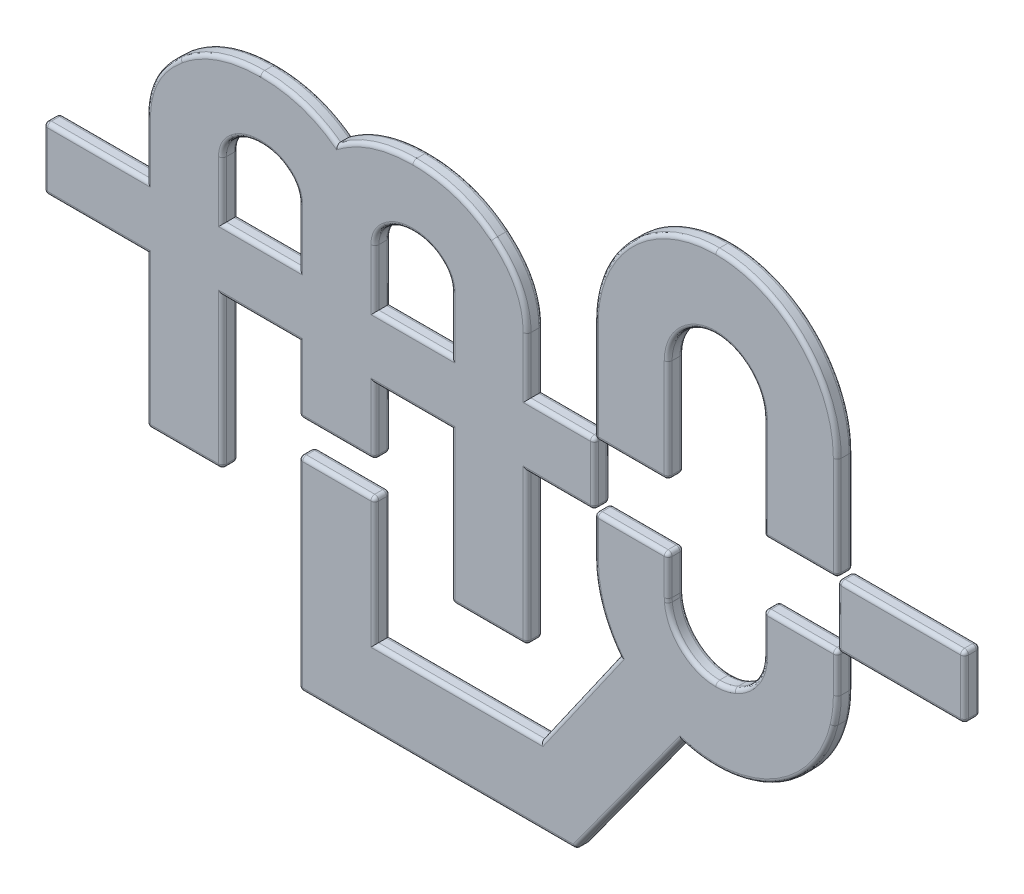
SolidWorks part; units mm, degrees
material "ABS"
ref_plane "Plano frontal" through (0, 0, 0) normal (0, 0, 1) x (1, 0, 0)
ref_plane "Plano superior" through (0, 0, 0) normal (0, 1, 0) x (1, 0, 0)
ref_plane "Plano direito" through (0, 0, 0) normal (1, 0, 0) x (0, 0, -1)
sketch "Esboço1" plane through (0, 0, 0) normal (0, 0, 1) x (1, 0, 0)
  line L0 (20.3706, -29.3615) -> (15.5406, -29.3604)
  line L3 (15.5406, -29.3604) -> (15.5406, -25.7678)
  line L4 (39.1028, -29.3604) -> (39.1028, -33.3385)
  line L5 (39.1028, -29.3604) -> (39.1028, -22.8429)
  line L6 (54.495, -33.3385) -> (62.5568, -33.3385)
  line L7 (62.5568, -33.3385) -> (62.5568, -29.3604)
  line L8 (62.5568, -29.3604) -> (54.495, -29.3604)
  line L9 (54.495, -33.3385) -> (54.495, -35.841)
  line L10 (44.6225, -43.2216) -> (37.8938, -52.503)
  line L11 (37.8938, -52.503) -> (20.3712, -52.5003)
  line L12 (20.3712, -52.5003) -> (20.3712, -39.5946)
  line L14 (-4.5162, 7.0505) -> (71.2838, 7.0505)
  line L15 (-4.5162, 7.0505) -> (-4.5162, -69.7495)
  line L16 (-4.5162, -69.7495) -> (71.2838, -69.7495)
  line L17 (71.2838, 7.0505) -> (71.2838, -69.7495)
  line L21 (16.0406, -28.8605) -> (16.0406, -25.7678)
  line L22 (19.8712, -25.7677) -> (19.8707, -28.8614)
  line L23 (19.8707, -28.8614) -> (16.0406, -28.8605)
  line L24 (25.6993, -25.7677) -> (25.7001, -28.8614)
  line L29 (-4.5162, 7.0505) -> (-4.5162, -69.7495)
  line L30 (-4.5162, -69.7495) -> (71.2838, -69.7495)
  line L31 (71.2838, -69.7495) -> (71.2838, 7.0505)
  line L32 (71.2838, 7.0505) -> (-4.5162, 7.0505)
  line L33 (25.7001, -28.8614) -> (29.53, -28.8605)
  line L34 (29.53, -28.8605) -> (29.53, -25.7678)
  line L35 (39.6028, -32.8385) -> (44.2804, -32.8385)
  line L36 (44.2804, -33.3385) -> (44.2804, -35.841)
  line L37 (49.3174, -35.841) -> (49.3174, -32.8385)
  line L38 (49.3174, -32.8385) -> (53.995, -32.8385)
  line L39 (53.995, -32.8385) -> (53.995, -29.8604)
  line L40 (53.995, -29.8604) -> (49.3174, -29.8604)
  line L41 (49.3174, -29.8604) -> (49.3174, -22.8429)
  line L42 (44.2804, -22.8429) -> (44.2804, -29.8604)
  line L43 (44.2804, -29.8604) -> (39.6028, -29.8604)
  line L44 (39.6028, -29.8604) -> (39.6028, -32.8385)
  line L45 (38.6028, -33.3385) -> (38.6028, -35.841)
  line L46 (40.0744, -40.5146) -> (35.4557, -47.1142)
  line L47 (35.4557, -47.1142) -> (25.6888, -47.1142)
  line L48 (25.6888, -47.1142) -> (25.6888, -39.0946)
  line L49 (19.8712, -39.0946) -> (25.6888, -39.0946)
  line L50 (19.8712, -53.0002) -> (19.8712, -39.0946)
  line L51 (38.1489, -53.003) -> (19.8712, -53.0002)
  line L52 (44.8242, -43.7952) -> (38.1489, -53.003)
  line L53 (54.995, -33.8385) -> (54.995, -35.841)
  line L54 (54.995, -33.8385) -> (63.0568, -33.8385)
  line L55 (63.0568, -33.8385) -> (63.0568, -28.8604)
  line L56 (63.0568, -28.8604) -> (54.995, -28.8604)
  line L57 (54.995, -22.8429) -> (54.995, -28.8604)
  line L58 (38.6028, -28.8604) -> (38.6028, -22.8429)
  line L59 (35.3396, -28.8604) -> (38.6028, -28.8604)
  line L60 (35.3396, -25.7678) -> (35.3396, -28.8604)
  line L61 (10.2309, -25.7678) -> (10.2309, -28.8604)
  line L62 (3.7108, -28.8604) -> (10.2309, -28.8604)
  line L63 (3.7108, -33.8385) -> (3.7108, -28.8604)
  line L64 (10.2309, -33.8385) -> (3.7108, -33.8385)
  line L65 (10.2309, -43.3732) -> (10.2309, -33.8385)
  line L66 (16.0406, -43.3732) -> (10.2309, -43.3732)
  line L67 (16.0406, -33.8385) -> (16.0406, -43.3732)
  line L68 (19.8707, -33.8389) -> (16.0406, -33.8385)
  line L69 (19.8713, -38.0277) -> (19.8707, -33.8389)
  line L70 (25.6992, -38.0277) -> (19.8713, -38.0277)
  line L71 (25.6992, -38.0277) -> (25.7001, -33.8389)
  line L72 (25.7001, -33.8389) -> (29.53, -33.8385)
  line L73 (29.53, -33.8385) -> (29.53, -43.3732)
  line L74 (29.53, -43.3732) -> (35.3396, -43.3732)
  line L75 (35.3396, -43.3732) -> (35.3396, -33.8385)
  line L76 (35.3396, -33.8385) -> (39.1028, -33.8385)
  line L77 (39.6028, -29.8604) -> (39.6028, -33.3385) construction
  line L78 (39.1028, -32.8385) -> (44.2804, -32.8385) construction
  line L79 (44.2804, -32.8385) -> (44.2804, -35.841) construction
  line L80 (44.2804, -33.3385) -> (44.2804, -32.8385)
  line L189 (20.3712, -25.7678) -> (20.3706, -29.3615)
  line L190 (25.2002, -29.3615) -> (30.03, -29.3604)
  line L192 (30.03, -29.3604) -> (30.03, -25.7678)
  line L193 (25.1993, -25.7678) -> (25.2002, -29.3615)
  line L194 (20.3712, -37.5277) -> (20.3712, -39.5946) construction
  line L195 (20.3712, -39.5946) -> (25.1888, -39.5946)
  line L196 (25.1888, -39.5946) -> (25.1993, -37.5277) construction
  line L197 (25.1993, -37.5277) -> (20.3712, -37.5277)
  line L198 (25.1993, -37.5277) -> (25.2002, -33.3389)
  line L209 (43.7804, -22.8429) -> (43.7804, -29.3604)
  line L210 (49.8174, -29.3604) -> (49.8174, -22.8429)
  line L211 (54.495, -29.3604) -> (49.8174, -29.3604)
  line L212 (54.495, -33.3385) -> (54.495, -29.3604)
  line L213 (49.8174, -33.3385) -> (54.495, -33.3385)
  line L214 (49.8174, -35.841) -> (49.8174, -33.3385)
  line L215 (43.7804, -33.3385) -> (43.7804, -35.841)
  line L216 (39.1028, -33.3385) -> (43.7804, -33.3385)
  line L217 (39.1028, -29.3604) -> (39.1028, -33.3385) construction
  line L218 (43.7804, -29.3604) -> (39.1028, -29.3604)
  line L219 (25.2002, -33.3389) -> (30.03, -33.3385)
  line L221 (30.03, -33.3385) -> (30.03, -42.8732)
  line L222 (30.03, -42.8732) -> (34.8396, -42.8732)
  line L223 (34.8396, -42.8732) -> (34.8396, -33.3385)
  line L225 (34.8396, -33.3385) -> (39.1028, -33.3385)
  line L226 (40.6893, -40.508) -> (35.716, -47.6142)
  line L227 (35.716, -47.6142) -> (25.1888, -47.6142)
  line L228 (25.1888, -47.6142) -> (25.1888, -39.5946)
  line L230 (20.3712, -37.5277) -> (20.3706, -33.3389)
  line L232 (39.1028, -33.3385) -> (39.1028, -35.841)
  line L233 (20.3706, -33.3389) -> (15.5406, -33.3385)
  line L234 (15.5406, -33.3385) -> (15.5406, -42.8732)
  line L235 (15.5406, -42.8732) -> (10.7309, -42.8732)
  line L236 (10.7309, -42.8732) -> (10.7309, -33.3385)
  line L238 (10.7309, -33.3385) -> (4.2108, -33.3385)
  line L239 (4.2108, -33.3385) -> (4.2108, -29.3604)
  line L240 (4.2108, -29.3604) -> (10.7309, -29.3604)
  line L241 (10.7309, -25.7678) -> (10.7309, -29.3604)
  line L242 (34.8396, -25.7678) -> (34.8396, -29.3604)
  line L243 (34.8396, -29.3604) -> (39.1028, -29.3604)
  line L244 (54.495, -22.8429) -> (54.495, -29.3604)
  spline S0 degree 1 poles (16.0406, -25.7678) (16.5619, -24.7584) knots 0 0 1 1 construction
  spline S1 degree 1 poles (16.5619, -24.7584) (17.9665, -24.2906) knots 0 0 1 1 construction
  spline S2 degree 1 poles (17.9665, -24.2906) (19.3573, -24.75) knots 0 0 1 1 construction
  spline S3 degree 1 poles (19.3573, -24.75) (19.8712, -25.7677) knots 0 0 1 1 construction
  spline S4 degree 3 poles (16.0406, -25.7678) (16.0406, -25.6734) (16.0617, -25.4788) (16.153, -25.2331) (16.3041, -24.9973) (16.4751, -24.8296) (16.5619, -24.7584) knots 8 8 8 8 8.249884 8.499767 8.749651 8.999535 8.999535 8.999535 8.999535
  spline S5 degree 3 poles (16.5619, -24.7584) (16.6555, -24.6821) (16.8576, -24.5445) (17.1847, -24.401) (17.5451, -24.3114) (17.8293, -24.2906) (17.9665, -24.2906) knots 9.000463 9.000463 9.000463 9.000463 9.250347 9.500232 9.750116 10 10 10 10
  spline S6 degree 3 poles (17.9665, -24.2906) (18.1005, -24.2906) (18.3773, -24.3109) (18.7336, -24.3986) (19.0598, -24.5397) (19.263, -24.675) (19.3573, -24.75) knots 10 10 10 10 10.24897 10.49794 10.74691 10.99588 10.99588 10.99588 10.99588
  spline S7 degree 3 poles (19.3573, -24.75) (19.4428, -24.8224) (19.6106, -24.9915) (19.76, -25.2299) (19.8504, -25.4781) (19.8712, -25.6731) (19.8712, -25.7677) knots 11.004142 11.004142 11.004142 11.004142 11.253098 11.502054 11.75101 11.999967 11.999967 11.999967 11.999967
  spline S11 degree 3 poles (44.6225, -43.2216) (45.3141, -43.4275) (46.0426, -43.5384) (46.7976, -43.5384) knots 10 10 10 10 11 11 11 11
  spline S12 degree 3 poles (54.2918, -37.5858) (54.4264, -37.0235) (54.495, -36.4402) (54.495, -35.841) knots 12 12 12 12 13 13 13 13
  spline S13 degree 3 poles (46.7976, -43.5384) (50.4325, -43.5384) (53.4999, -40.9884) (54.2918, -37.5858) knots 11 11 11 11 12 12 12 12
  spline S14 degree 1 poles (28.9981, -24.7504) (29.53, -25.7678) knots 0 0 1 1 construction
  spline S15 degree 1 poles (27.6041, -24.2906) (28.9981, -24.7504) knots 0 0 1 1 construction
  spline S16 degree 1 poles (26.2233, -24.7584) (27.6041, -24.2906) knots 0 0 1 1 construction
  spline S17 degree 1 poles (25.6993, -25.7677) (26.2233, -24.7584) knots 0 0 1 1 construction
  spline S18 degree 3 poles (29.53, -25.7678) (29.53, -25.6736) (29.5088, -25.4796) (29.4162, -25.2326) (29.2621, -24.994) (29.0869, -24.823) (28.9981, -24.7504) knots 17.999964 17.999964 17.999964 17.999964 18.249973 18.499982 18.749991 19 19 19 19
  spline S19 degree 3 poles (28.9981, -24.7504) (28.9066, -24.6755) (28.7091, -24.5411) (28.3854, -24.3996) (28.0264, -24.3113) (27.7415, -24.2906) (27.6041, -24.2906) knots 17 17 17 17 17.250009 17.500019 17.750028 18.000037 18.000037 18.000037 18.000037
  spline S20 degree 3 poles (27.6041, -24.2906) (27.4703, -24.2906) (27.1933, -24.3113) (26.84, -24.4005) (26.5178, -24.5436) (26.3164, -24.6821) (26.2233, -24.7584) knots 15.999619 15.999619 15.999619 15.999619 16.249714 16.499809 16.749905 17 17 17 17
  spline S21 degree 3 poles (26.2233, -24.7584) (26.1359, -24.8296) (25.9636, -24.9976) (25.812, -25.2332) (25.7205, -25.4786) (25.6993, -25.6734) (25.6993, -25.7677) knots 15.000046 15.000046 15.000046 15.000046 15.25013 15.500213 15.750297 16.00038 16.00038 16.00038 16.00038
  spline S22 degree 1 poles (44.2893, -36.0356) (46.7976, -38.3608) knots 0 0 1 1 construction
  spline S23 degree 1 poles (46.7976, -38.3608) (47.7651, -38.1567) knots 0 0 1 1 construction
  spline S24 degree 1 poles (47.7651, -38.1567) (48.8378, -37.2916) knots 0 0 1 1 construction
  spline S25 degree 1 poles (48.8378, -37.2916) (49.3174, -35.841) knots 0 0 1 1 construction
  spline S26 degree 1 poles (49.3174, -22.8429) (46.7976, -20.3257) knots 0 0 1 1 construction
  spline S27 degree 1 poles (46.7976, -20.3257) (44.2804, -22.8429) knots 0 0 1 1 construction
  spline S28 degree 3 poles (44.2893, -36.0356) (44.3144, -36.3459) (44.4904, -36.9638) (45.0612, -37.7175) (45.8506, -38.2323) (46.485, -38.3608) (46.7976, -38.3608) knots 3 3 3 3 3.25 3.5 3.75 4 4 4 4
  spline S29 degree 3 poles (46.7976, -38.3608) (46.8823, -38.3608) (47.0527, -38.3518) (47.2991, -38.3123) (47.5379, -38.2482) (47.6904, -38.1897) (47.7651, -38.1567) knots 2 2 2 2 2.250601 2.501202 2.751803 3.002404 3.002404 3.002404 3.002404
  spline S30 degree 3 poles (47.7651, -38.1567) (47.8715, -38.1112) (48.0783, -38.0051) (48.3631, -37.8046) (48.6198, -37.567) (48.7693, -37.3862) (48.8378, -37.2916) knots 0.998307 0.998307 0.998307 0.998307 1.248951 1.499594 1.750238 2.000882 2.000882 2.000882 2.000882
  spline S31 degree 3 poles (48.8378, -37.2916) (48.9134, -37.1884) (49.0493, -36.9705) (49.2006, -36.6157) (49.2953, -36.2398) (49.3174, -35.973) (49.3174, -35.841) knots -0.000798 -0.000798 -0.000798 -0.000798 0.249401 0.499601 0.7498 1 1 1 1
  spline S32 degree 3 poles (49.3174, -22.8429) (49.3174, -22.5151) (49.1758, -21.85) (48.6107, -21.0332) (47.7938, -20.4678) (47.1263, -20.3257) (46.7976, -20.3257) knots 5 5 5 5 5.25 5.5 5.75 6 6 6 6
  spline S33 degree 3 poles (46.7976, -20.3257) (46.4699, -20.3257) (45.805, -20.4676) (44.9879, -21.0332) (44.4223, -21.8503) (44.2804, -22.5152) (44.2804, -22.8429) knots 4 4 4 4 4.25 4.5 4.75 5 5 5 5
  spline S34 degree 1 poles (38.6028, -35.841) (40.0744, -40.5146) knots 0 0 1 1 construction
  spline S35 degree 1 poles (44.8242, -43.7952) (46.7976, -44.0384) knots 0 0 1 1 construction
  spline S36 degree 1 poles (46.7976, -44.0384) (54.7784, -37.7007) knots 0 0 1 1 construction
  spline S37 degree 1 poles (54.7784, -37.7007) (54.995, -35.841) knots 0 0 1 1 construction
  spline S38 degree 1 poles (54.995, -22.8429) (46.7976, -14.6455) knots 0 0 1 1 construction
  spline S39 degree 1 poles (46.7976, -14.6455) (38.6028, -22.8429) knots 0 0 1 1 construction
  spline S40 degree 1 poles (35.3396, -25.7678) (33.0399, -21.1789) knots 0 0 1 1 construction
  spline S41 degree 1 poles (33.0399, -21.1789) (27.6041, -19.3257) knots 0 0 1 1 construction
  spline S42 degree 1 poles (27.6041, -19.3257) (22.7774, -20.7304) knots 0 0 1 1 construction
  spline S43 degree 1 poles (22.7774, -20.7304) (17.9665, -19.3257) knots 0 0 1 1 construction
  spline S44 degree 1 poles (17.9665, -19.3257) (12.5201, -21.1868) knots 0 0 1 1 construction
  spline S45 degree 1 poles (12.5201, -21.1868) (10.2309, -25.7678) knots 0 0 1 1 construction
  spline S46 degree 3 poles (38.6028, -35.841) (38.6028, -36.2666) (38.6708, -37.127) (38.9618, -38.3404) (39.4271, -39.4836) (39.842, -40.1819) (40.0744, -40.5146) knots 8 8 8 8 8.232322 8.464643 8.696965 8.929287 8.929287 8.929287 8.929287
  spline S47 degree 3 poles (44.8242, -43.7952) (44.983, -43.835) (45.3021, -43.9049) (45.7922, -43.9813) (46.2897, -44.0279) (46.6288, -44.0384) (46.7976, -44.0384) knots 10.154566 10.154566 10.154566 10.154566 10.365924 10.577283 10.788641 11 11 11 11
  spline S48 degree 3 poles (46.7976, -44.0384) (47.2727, -44.0384) (48.2341, -43.9535) (50.023, -43.4727) (52.0199, -42.3385) (53.8396, -40.3149) (54.5717, -38.588) (54.7784, -37.7007) knots 11 11 11 11 11.124982 11.249965 11.499929 11.749894 11.999858 11.999858 11.999858 11.999858
  spline S49 degree 3 poles (54.7784, -37.7007) (54.8144, -37.5503) (54.8773, -37.2478) (54.9451, -36.7854) (54.9859, -36.3172) (54.995, -35.9993) (54.995, -35.841) knots 12.000855 12.000855 12.000855 12.000855 12.250641 12.500427 12.750214 13 13 13 13
  spline S50 degree 3 poles (54.995, -22.8429) (54.995, -22.2913) (54.8799, -21.173) (54.2328, -19.1241) (52.7306, -16.9123) (50.5191, -15.4087) (48.4693, -14.7608) (47.3498, -14.6455) (46.7976, -14.6455) knots 9 9 9 9 9.125 9.25 9.5 9.75 9.875 10 10 10 10
  spline S51 degree 3 poles (46.7976, -14.6455) (46.2462, -14.6455) (45.1284, -14.7608) (43.0803, -15.4088) (40.8692, -16.9122) (39.366, -19.124) (38.7181, -21.1728) (38.6028, -22.2912) (38.6028, -22.8429) knots 0 0 0 0 0.125 0.25 0.5 0.75 0.875 1 1 1 1
  spline S52 degree 3 poles (35.3396, -25.7678) (35.3396, -25.3317) (35.2442, -24.4477) (34.8032, -23.2407) (34.0867, -22.1466) (33.4, -21.4745) (33.0399, -21.1789) knots 22 22 22 22 22.24999 22.49998 22.74997 22.99996 22.99996 22.99996 22.99996
  spline S53 degree 3 poles (33.0399, -21.1789) (32.6697, -20.8746) (31.8715, -20.3276) (30.5631, -19.7489) (29.1512, -19.4017) (28.1132, -19.3257) (27.6041, -19.3257) knots 0.00004 0.00004 0.00004 0.00004 0.25003 0.50002 0.75001 1 1 1 1
  spline S54 degree 3 poles (27.6041, -19.3257) (27.1621, -19.3257) (26.2635, -19.3834) (25.02, -19.6463) (23.849, -20.0851) (23.1221, -20.498) (22.7774, -20.7304) knots 1 1 1 1 1.233058 1.466117 1.699175 1.932234 1.932234 1.932234 1.932234
  spline S55 degree 3 poles (22.7774, -20.7304) (22.4351, -20.4978) (21.7131, -20.085) (20.5466, -19.6461) (19.3062, -19.3834) (18.4081, -19.3257) (17.9665, -19.3257) knots 2.068142 2.068142 2.068142 2.068142 2.301106 2.534071 2.767035 3 3 3 3
  spline S56 degree 3 poles (17.9665, -19.3257) (17.4571, -19.3257) (16.4187, -19.4021) (15.0048, -19.751) (13.6935, -20.332) (12.8919, -20.8815) (12.5201, -21.1868) knots 3 3 3 3 3.250001 3.500003 3.750004 4.000005 4.000005 4.000005 4.000005
  spline S57 degree 3 poles (12.5201, -21.1868) (12.1616, -21.4814) (11.4785, -22.151) (10.7651, -23.243) (10.326, -24.4483) (10.2309, -25.3319) (10.2309, -25.7678) knots 3.999995 3.999995 3.999995 3.999995 4.249996 4.499997 4.749999 5 5 5 5
  spline S58 degree 1 poles (44.2804, -35.841) (44.2883, -36.0244) knots 0 0 1 1 construction
  spline S59 degree 3 poles (44.2804, -35.841) (44.2804, -35.8572) (44.2807, -35.8899) (44.2821, -35.9379) (44.2846, -35.9841) (44.2869, -36.0106) (44.2883, -36.0244) knots 4 4 4 4 4.25 4.5 4.75 5 5 5 5
  spline S342 degree 3 poles (49.8174, -22.8429) (49.8174, -21.2089) (48.4369, -19.8257) (46.7976, -19.8257) knots 5 5 5 5 6 6 6 6
  spline S343 degree 3 poles (46.7976, -19.8257) (45.1636, -19.8257) (43.7804, -21.2089) (43.7804, -22.8429) knots 4 4 4 4 5 5 5 5
  spline S344 degree 3 poles (49.242, -37.5858) (49.6036, -37.0922) (49.8174, -36.4877) (49.8174, -35.841) knots 0 0 0 0 1 1 1 1
  spline S345 degree 3 poles (47.9644, -38.6153) (48.4765, -38.3962) (48.9173, -38.0346) (49.242, -37.5858) knots 1 1 1 1 2 2 2 2
  spline S346 degree 3 poles (46.7976, -38.8608) (47.2094, -38.8608) (47.6054, -38.7737) (47.9644, -38.6153) knots 2 2 2 2 3 3 3 3
  spline S347 degree 3 poles (43.791, -36.0759) (43.915, -37.6096) (45.2402, -38.8608) (46.7976, -38.8608) knots 3 3 3 3 4 4 4 4
  spline S348 degree 3 poles (43.7804, -35.841) (43.7804, -35.9175) (43.783, -35.9994) (43.791, -36.0759) knots 4 4 4 4 5 5 5 5
  spline S359 degree 3 poles (19.6744, -24.3634) (20.139, -24.7541) (20.3712, -25.2213) (20.3712, -25.7678) knots 11 11 11 11 12 12 12 12
  spline S360 degree 3 poles (17.9665, -23.7906) (18.6291, -23.7906) (19.1992, -23.9833) (19.6744, -24.3634) knots 10 10 10 10 11 11 11 11
  spline S361 degree 3 poles (15.5406, -25.7678) (15.5406, -25.2213) (15.7755, -24.7567) (16.2454, -24.3713) knots 8 8 8 8 9 9 9 9
  spline S362 degree 3 poles (16.2454, -24.3713) (16.7179, -23.9859) (17.2907, -23.7906) (17.9665, -23.7906) knots 9 9 9 9 10 10 10 10
  spline S371 degree 3 poles (39.1028, -35.841) (39.1028, -37.5885) (39.6941, -39.2119) (40.6893, -40.508) knots 8 8 8 8 9 9 9 9
  spline S376 degree 3 poles (29.3147, -24.3634) (29.7925, -24.7541) (30.03, -25.2213) (30.03, -25.7678) knots 18 18 18 18 19 19 19 19
  spline S377 degree 3 poles (27.6041, -23.7906) (28.2799, -23.7906) (28.8501, -23.9833) (29.3147, -24.3634) knots 17 17 17 17 18 18 18 18
  spline S378 degree 3 poles (25.1993, -25.7678) (25.1993, -25.2213) (25.4343, -24.7567) (25.9068, -24.3713) knots 15 15 15 15 16 16 16 16
  spline S379 degree 3 poles (25.9068, -24.3713) (26.3766, -23.9859) (26.9416, -23.7906) (27.6041, -23.7906) knots 16 16 16 16 17 17 17 17
  spline S411 degree 3 poles (34.8396, -25.7678) (34.8396, -24.1232) (34.1348, -22.7241) (32.7226, -21.5653) knots 22 22 22 22 23 23 23 23
  spline S412 degree 3 poles (32.7226, -21.5653) (31.3129, -20.4065) (29.605, -19.8257) (27.6041, -19.8257) knots 0 0 0 0 1 1 1 1
  spline S413 degree 3 poles (27.6041, -19.8257) (25.751, -19.8257) (24.1408, -20.3325) (22.7761, -21.3436) knots 1 1 1 1 2 2 2 2
  spline S414 degree 3 poles (22.7761, -21.3436) (21.4245, -20.3325) (19.8196, -19.8257) (17.9665, -19.8257) knots 2 2 2 2 3 3 3 3
  spline S415 degree 3 poles (17.9665, -19.8257) (15.9655, -19.8257) (14.255, -20.4091) (12.8375, -21.5732) knots 3 3 3 3 4 4 4 4
  spline S416 degree 3 poles (12.8375, -21.5732) (11.4332, -22.7268) (10.7309, -24.1232) (10.7309, -25.7678) knots 4 4 4 4 5 5 5 5
  spline S417 degree 3 poles (46.7976, -15.1455) (42.5688, -15.1455) (39.1028, -18.6114) (39.1028, -22.8429) knots 0 0 0 0 1 1 1 1
  spline S418 degree 3 poles (54.495, -22.8429) (54.495, -18.6114) (51.0344, -15.1455) (46.7976, -15.1455) knots 9 9 9 9 10 10 10 10
  dimension "D9" = 0.5
  dimension "D10" = 0.5
  dimension "D11" = 0.5
extrude "Ressalto-extrusão1" add sketch "Esboço1" along normal blind 1 contours S415 S416 L241 L240 L239 L238 L236 L235 L234 L233 L230 L197 L198 L219 L221 L222 L223 L225 L4 L243 L242 S411 S412 S413 S414 S361 S362 S360 S359 L189 L0 L3 S378 S379 S377 S376 L192 L190 L193 | L244 S418 S417 L5 L218 L209 S343 S342 L210 L211 | L232 S371 L226 L227 L228 L195 L12 L11 L10 S11 S13 S12 L9 L213 L214 S344 S345 S346 S347 S348 L215 L216 | L212 L6 L7 L8 region at (39.3123, -26.1017, 0) region at (22.4016, -30.4014, 0) region at (41.4416, -33.7299, 0) region at (58.5259, -31.3495, 0)
fillet "Filete1" radius 0.25 89 edges at (20.3709, -27.5646, 0) (17.9556, -29.361, 0) (15.5406, -27.5641, 0) (30.03, -27.5641, 0) (27.6151, -29.361, 0) (25.1998, -27.5646, 0) (10.7309, -27.5641, 0) (7.4709, -29.3604, 0) (4.2108, -31.3495, 0) (7.4709, -33.3385, 0) (10.7309, -38.1058, 0) (13.1357, -42.8732, 0) (15.5406, -38.1058, 0) (17.9556, -33.3387, 0) (20.3709, -35.4333, 0) (22.7853, -37.5277, 0) (25.1998, -35.4333, 0) (27.6151, -33.3387, 0) (30.03, -38.1058, 0) (32.4348, -42.8732, 0) (34.8396, -38.1058, 0) (36.9712, -33.3385, 0) (39.1028, -31.3495, 0) (36.9712, -29.3604, 0) (34.8396, -27.5641, 0) (20.3709, -27.5646, 1) (17.9556, -29.361, 1) (15.5406, -27.5641, 1) (30.03, -27.5641, 1) (27.6151, -29.361, 1) (25.1998, -27.5646, 1) (10.7309, -27.5641, 1) (7.4709, -29.3604, 1) (4.2108, -31.3495, 1) (7.4709, -33.3385, 1) (10.7309, -38.1058, 1) (13.1357, -42.8732, 1) (15.5406, -38.1058, 1) (17.9556, -33.3387, 1) (20.3709, -35.4333, 1) (22.7853, -37.5277, 1) (25.1998, -35.4333, 1) (27.6151, -33.3387, 1) (30.03, -38.1058, 1) (32.4348, -42.8732, 1) (34.8396, -38.1058, 1) (36.9712, -33.3385, 1) (39.1028, -31.3495, 1) (36.9712, -29.3604, 1) (34.8396, -27.5641, 1) (25.9068, -24.3713, 0.5) (39.1028, -29.3604, 0.5) (39.1028, -33.3385, 0.5) (34.8396, -42.8732, 0.5) (30.03, -42.8732, 0.5) (25.1993, -37.5277, 0.5) (20.3712, -37.5277, 0.5) (15.5406, -42.8732, 0.5) (10.7309, -42.8732, 0.5) (4.2108, -33.3385, 0.5) (4.2108, -29.3604, 0.5)
fillet "Filete2" radius 0.25 24 edges at (54.495, -26.1017, 0) (39.1028, -26.1017, 0) (41.4416, -29.3604, 0) (43.7804, -26.1017, 0) (49.8174, -26.1017, 0) (52.1562, -29.3604, 0) (54.495, -26.1017, 1) (39.1028, -26.1017, 1) (41.4416, -29.3604, 1) (43.7804, -26.1017, 1) (49.8174, -26.1017, 1) (52.1562, -29.3604, 1) (54.495, -29.3604, 0.5) (49.8174, -29.3604, 0.5) (43.7804, -29.3604, 0.5) (39.1028, -29.3604, 0.5)
fillet "Filete3" radius 0.25 12 edges at (54.495, -31.3495, 0) (58.5259, -33.3385, 0) (62.5568, -31.3495, 0) (58.5259, -29.3604, 0) (58.5259, -33.3385, 1) (62.5568, -31.3495, 1) (58.5259, -29.3604, 1) (54.495, -29.3604, 0.5) (62.5568, -29.3604, 0.5) (62.5568, -33.3385, 0.5) (54.495, -33.3385, 0.5) (54.495, -31.3495, 1)
fillet "Filete4" radius 0.25 55 edges at (39.1028, -34.5897, 0) (38.2027, -44.0611, 0) (30.4524, -47.6142, 0) (25.1888, -43.6044, 0) (22.78, -39.5946, 0) (20.3712, -46.0475, 0) (29.1325, -52.5016, 0) (41.2581, -47.8623, 0) (54.495, -34.5897, 0) (52.1562, -33.3385, 0) (49.8174, -34.5897, 0) (43.7804, -34.5897, 0) (41.4416, -33.3385, 0) (39.1028, -34.5897, 1) (38.2027, -44.0611, 1) (30.4524, -47.6142, 1) (25.1888, -43.6044, 1) (22.78, -39.5946, 1) (20.3712, -46.0475, 1) (29.1325, -52.5016, 1) (41.2581, -47.8623, 1) (54.495, -34.5897, 1) (49.8174, -34.5897, 1) (43.7804, -34.5897, 1) (41.4416, -33.3385, 1) (39.1028, -33.3385, 0.5) (43.7804, -33.3385, 0.5) (43.791, -36.0759, 0.5) (47.9644, -38.6153, 0.5) (49.242, -37.5858, 0.5) (49.8174, -33.3385, 0.5) (54.495, -33.3385, 0.5) (37.8938, -52.503, 0.5) (20.3712, -52.5003, 0.5) (20.3712, -39.5946, 0.5) (25.1888, -39.5946, 0.5) (52.1562, -33.3385, 1)
